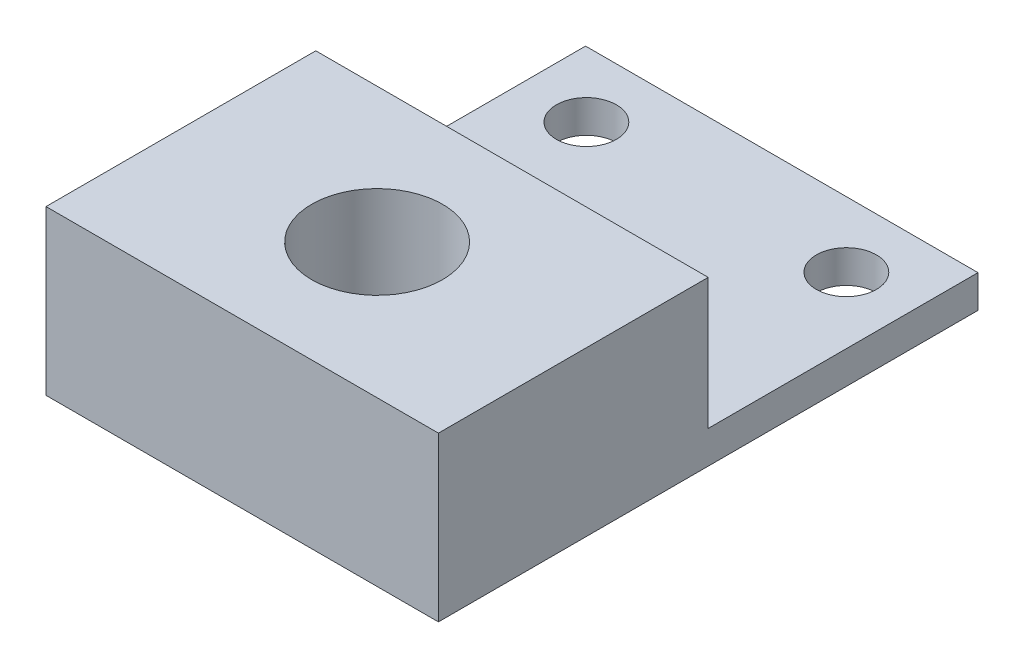
SolidWorks part; units mm, degrees
ref_plane "Front Plane" through (0, 0, 0) normal (0, 0, 1) x (1, 0, 0)
ref_plane "Top Plane" through (0, 0, 0) normal (0, 1, 0) x (1, 0, 0)
ref_plane "Right Plane" through (0, 0, 0) normal (1, 0, 0) x (0, 0, -1)
sketch "Sketch2" plane through (0, 0, 0) normal (0, 1, 0) x (1, 0, 0)
  line L0 (-12, 0) -> (12, -16.5) construction
  line L1 (12, -16.5) -> (-12, -16.5)
  line L2 (12, -16.5) -> (12, 16.5)
  line L3 (12, 16.5) -> (-12, 16.5)
  line L4 (-12, -16.5) -> (-12, 16.5)
  line L5 (12, -16.5) -> (-12, 16.5) construction
  line L6 (12, 16.5) -> (-12, -16.5) construction
  line L7 (12, 0) -> (-12, -16.5) construction
  line L8 (0, 0) -> (0, 16.5) construction
  line L9 (-12, 0) -> (12, 0)
  circle A0 centre (0, -8.25) radius 4
  circle A1 centre (-7.95, 12.5) radius 1.835
  circle A2 centre (7.95, 12.5) radius 1.835
  point P0 (0, 0)
  dimension "D3" = 8
  dimension "D4" = 3.67
  dimension "D5" = 7.95
  dimension "D6" = 4
  dimension "D1" = 24
  dimension "D2" = 33
extrude "Boss-Extrude1" add sketch "Sketch2" along normal blind 10 contours L9 L4 L1 L2 A0 region at (0, 0, 16.2088)
extrude "Boss-Extrude2" add sketch "Sketch2<3>" along normal blind 2 contours L4 L9 L2 L3 A1 A2 region at (0, 0, -8.0101)
sketch "Sketch2<3>" plane through (0, 0, 0) normal (0, 1, 0) x (1, 0, 0) same geometry as "Sketch2"
